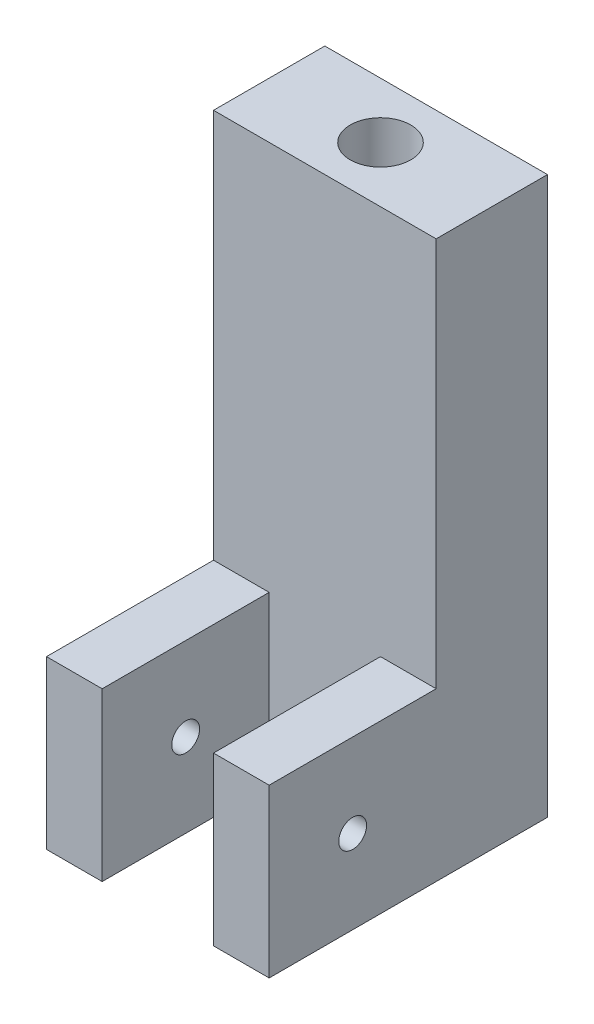
SolidWorks part; units mm, degrees
ref_plane "Front Plane" through (0, 0, 0) normal (0, 0, 1) x (1, 0, 0)
ref_plane "Top Plane" through (0, 0, 0) normal (0, 1, 0) x (1, 0, 0)
ref_plane "Right Plane" through (0, 0, 0) normal (1, 0, 0) x (0, 0, -1)
sketch "Sketch1" plane through (0, 0, 0) normal (1, 0, 0) x (0, 0, -1)
  line L2 (0, 0) -> (0, 63.5)
  line L3 (0, 63.5) -> (-12.7, 63.5)
  line L4 (-12.7, 19.05) -> (-12.7, 63.5)
  line L5 (0, 0) -> (-31.75, 0)
  line L7 (-12.7, 19.05) -> (-31.75, 19.05)
  line L8 (-31.75, 0) -> (-31.75, 19.05)
  dimension "D1" = 63.5
  dimension "D2" = 19.05
  dimension "D3" = 12.7
  dimension "D4" = 31.75
extrude "Boss-Extrude1" add sketch "Sketch1" along normal blind 25.4
sketch "Sketch2" plane through (25.4, 0, 0) normal (1, 0, 0) x (0, 0, -1)
  line L0 (-31.75, 19.05) -> (-31.75, 0) construction
  line L1 (-12.7, 19.05) -> (-31.75, 19.05) construction
  circle A0 centre (-22.225, 9.525) radius 1.5875
  dimension "D3" = 3.175
  dimension "D1" = 9.525
  dimension "D2" = 9.525
extrude "Cut-Extrude1" cut sketch "Sketch2" against normal through all
sketch "Sketch3" plane through (0, 0, 31.75) normal (0, 0, 1) x (1, 0, 0)
  line L0 (25.4, 0) -> (0, 0) construction
  line L1 (6.35, 0) -> (19.05, 0)
  line L2 (6.35, 0) -> (6.35, 19.05)
  line L3 (6.35, 19.05) -> (19.05, 19.05)
  line L4 (19.05, 0) -> (19.05, 19.05)
  line L5 (25.4, 19.05) -> (0, 19.05) construction
  line L6 (0, 19.05) -> (0, 0) construction
  dimension "D1" = 12.7
  dimension "D2" = 6.35
extrude "Cut-Extrude2" cut sketch "Sketch3" against normal blind 19.05
hole_wizard "5/16-24 Tapped Hole1" positions "Sketch4" profile "Sketch5" tap size "5/16-24" standard "ANSI Inch" end condition through all
sketch "Sketch4" plane through (0, 63.5, 0) normal (0, 1, 0) x (1, 0, 0)
  line L0 (0, -6.35) -> (25.4, -6.35) construction
  line L1 (0, 0) -> (0, -12.7) construction
  line L2 (25.4, 0) -> (25.4, -12.7) construction
  point P0 (12.7, -6.35)
cosmetic thread "Hole Thread1" parameters "D1"=25.4, "D2"=7.9375
sketch "Sketch5" plane through (12.7, 63.5, 6.35) normal (1, 0, 0) x (0, 0, 1)
  line L0 (0, 0) -> (0, 63.5)
  line L1 (0, 63.5) -> (3.4544, 63.5)
  line L2 (3.4544, 63.5) -> (3.4544, 0)
  line L5 (3.4544, 0) -> (0, 0)
  line L11 (0, -6.35) -> (0, 107.95) construction
  dimension "Thru Tap Drill Dia." = 6.9088
  dimension "Thru Tap Drill Depth" = 63.5
